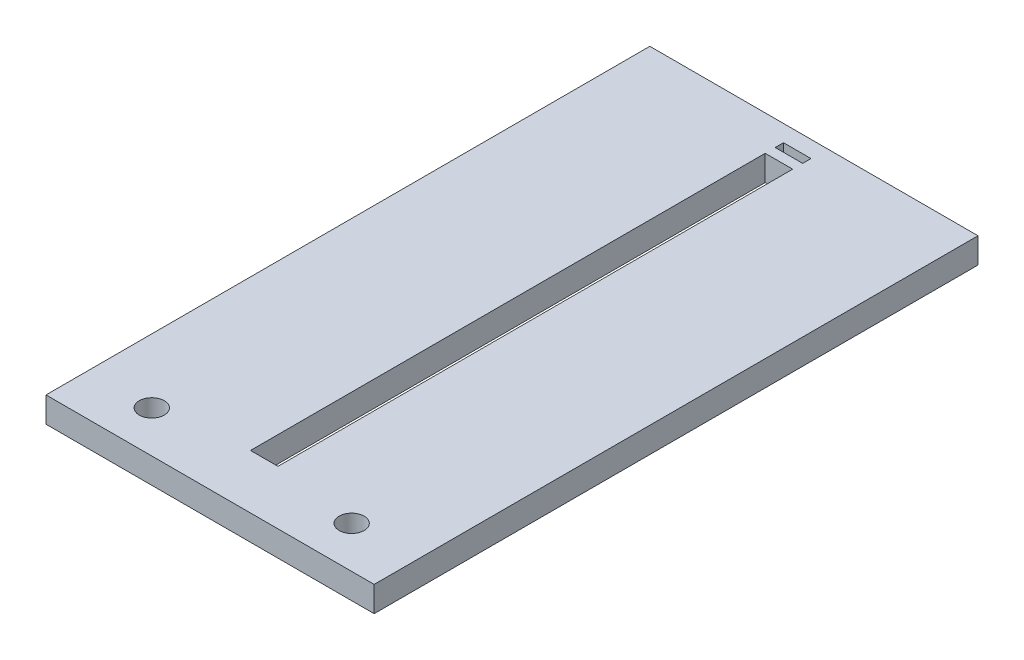
SolidWorks part; units mm, degrees
ref_plane "Front Plane" through (0, 0, 0) normal (0, 0, 1) x (1, 0, 0)
ref_plane "Top Plane" through (0, 0, 0) normal (0, 1, 0) x (1, 0, 0)
ref_plane "Right Plane" through (0, 0, 0) normal (1, 0, 0) x (0, 0, -1)
sketch "Sketch1" plane through (0, 0, 0) normal (0, 1, 0) x (1, 0, 0)
  line L1 (-19.7, 0) -> (19.7, 0)
  line L2 (-19.7, 0) -> (-19.7, 72.5)
  line L3 (-19.7, 72.5) -> (19.7, 72.5)
  line L4 (19.7, 0) -> (19.7, 72.5)
  point P5 (0, 0)
  dimension "D1" = 39.4
  dimension "D2" = 72.5
extrude "Boss-Extrude1" add sketch "Sketch1" along normal blind 3.05 contours L2 | L1 L4 L3 L2 | L4 region at (0, 0, -36.25)
sketch "Sketch4" plane through (0, 3.05, 0) normal (0, 1, 0) x (1, 0, 0)
  line L0 (-19.7, 72.5) -> (19.7, 72.5) construction
  line L2 (-19.7, 0) -> (19.7, 0) construction
  line L3 (1.65, 70.5) -> (-1.65, 70.5)
  line L4 (-1.65, 70.5) -> (-1.65, 69.5)
  line L5 (-1.65, 69.5) -> (1.65, 69.5)
  line L6 (1.65, 69.5) -> (1.65, 70.5)
  line L7 (0, 0) -> (0, 72.5) construction
  line L9 (1.65, 68.3) -> (-1.65, 68.3)
  line L10 (-1.65, 68.3) -> (-1.65, 6.5)
  line L11 (-1.65, 6.5) -> (1.65, 6.5)
  line L12 (1.65, 6.5) -> (1.65, 68.3)
  point P6 (0, 6.5)
  point P10 (0, 70.5)
  point P22 (0, 68.3)
  dimension "D1" = 2
  dimension "D2" = 1
  dimension "D3" = 1.2
  dimension "D4" = 3.3
  dimension "D7" = 6.5
extrude "Cut-Extrude1" cut sketch "Sketch4" against normal through all contours L5 L7 L3 L4 | L11 L7 L9 L10 | L7 L11 L12 L9 | L7 L5 L6 L3 | L6 L3 L4 L5 region at (0.825, 3.05, -70) region at (0.825, 3.05, -37.4) region at (-0.825, 3.05, -37.4) region at (-0.825, 3.05, -70)
sketch "Sketch7" plane through (0, 3.05, 0) normal (0, 1, 0) x (1, 0, 0)
  line L0 (0, 0) -> (-12, 0)
  line L1 (-19.7, 0) -> (19.7, 0) construction
  line L2 (-12, 0) -> (-12, 5)
  line L4 (0, 0) -> (0, 70) construction
  circle A0 centre (-12, 5) radius 1.5
  circle A2 centre (12, 5) radius 1.5
  dimension "D3" = 3
  dimension "D1" = 12
  dimension "D2" = 5
extrude "Cut-Extrude4" cut sketch "Sketch7" against normal through all contours A0 L2 | L2 A0 | A2 region at (-10.9693, 3.05, -3.9693)
